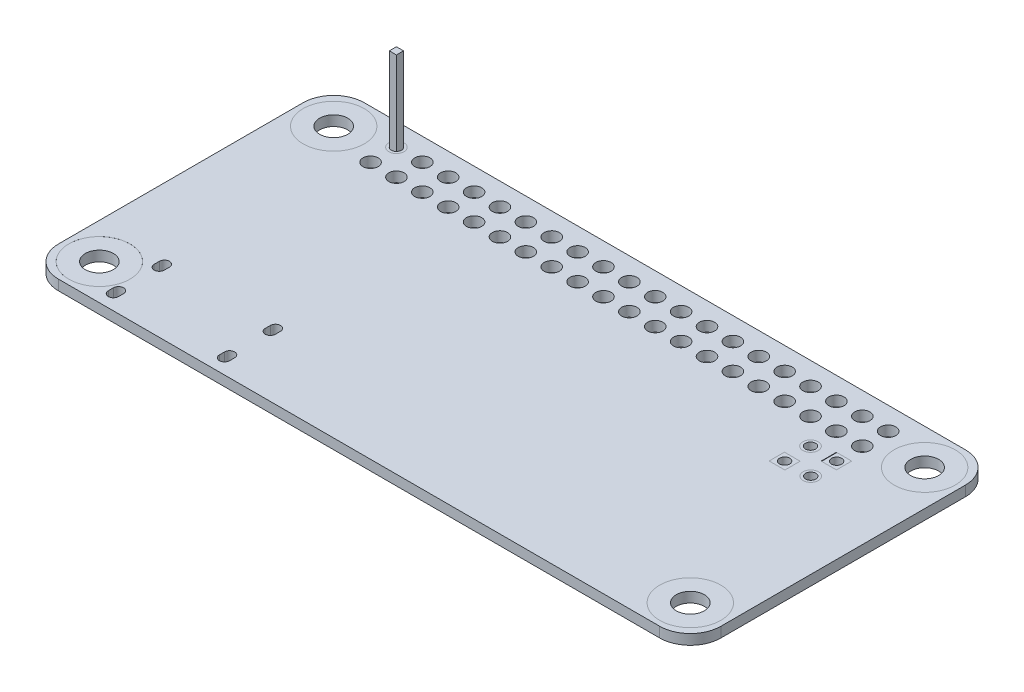
SolidWorks part; units mm, degrees
ref_plane "Front Plane" through (0, 0, 0) normal (0, 0, 1) x (1, 0, 0)
ref_plane "Top Plane" through (0, 0, 0) normal (0, 1, 0) x (1, 0, 0)
ref_plane "Right Plane" through (0, 0, 0) normal (1, 0, 0) x (0, 0, -1)
sketch "Sketch1" plane through (0, 0, 0) normal (0, 1, 0) x (1, 0, 0)
  line L0 (-27.4768, 39.9178) -> (-27.4768, -37.6558) construction
  line L1 (-29.5, -15) -> (29.5, -15)
  line L2 (-32.5, -12) -> (-32.5, 12)
  line L3 (-29.5, 15) -> (29.5, 15)
  line L4 (32.5, -12) -> (32.5, 12)
  line L5 (-32.5, -15) -> (32.5, 15) construction
  line L6 (-32.5, 15) -> (32.5, -15) construction
  line L7 (0, 0) -> (0, 39.9178) construction
  line L9 (-25.5, 14.1112) -> (25.5, 14.1112) construction
  line L10 (-25.5, 14.1112) -> (-25.5, 8.9112) construction
  line L11 (-25.5, 8.9112) -> (25.5, 8.9112) construction
  line L12 (25.5, 14.1112) -> (25.5, 8.9112) construction
  line L13 (23.38, 6.9577) -> (24.88, 6.9577)
  line L14 (23.38, 6.9577) -> (23.38, 8.4577)
  line L15 (23.38, 8.4577) -> (24.88, 8.4577)
  line L16 (24.88, 6.9577) -> (24.88, 8.4577)
  line L17 (23.38, 6.9577) -> (24.88, 8.4577) construction
  line L18 (23.38, 8.4577) -> (24.88, 6.9577) construction
  line L19 (20.8606, 4.4177) -> (22.3606, 4.4177)
  line L20 (20.8606, 4.4177) -> (20.8606, 5.9177)
  line L21 (20.8606, 5.9177) -> (22.3606, 5.9177)
  line L22 (22.3606, 4.4177) -> (22.3606, 5.9177)
  line L23 (20.8606, 4.4177) -> (22.3606, 5.9177) construction
  line L24 (20.8606, 5.9177) -> (22.3606, 4.4177) construction
  arc A0 (-32.5, 12) -> (-29.5, 15) centre (-29.5, 12) cw
  arc A1 (-29.5, -15) -> (-32.5, -12) centre (-29.5, -12) cw
  arc A2 (29.5, -15) -> (32.5, -12) centre (29.5, -12) ccw
  arc A3 (29.5, 15) -> (32.5, 12) centre (29.5, 12) cw
  circle A4 centre (-29, 11.5) radius 3
  circle A5 centre (-29, -11.5) radius 3
  circle A6 centre (29, -11.5) radius 3
  circle A7 centre (-24.13, 12.7877) radius 0.75
  circle A8 centre (-21.59, 12.7877) radius 0.75
  circle A9 centre (-19.05, 12.7877) radius 0.75
  circle A10 centre (-16.51, 12.7877) radius 0.75
  circle A11 centre (-13.97, 12.7877) radius 0.75
  circle A12 centre (-11.43, 12.7877) radius 0.75
  circle A13 centre (-8.89, 12.7877) radius 0.75
  circle A14 centre (-6.35, 12.7877) radius 0.75
  circle A15 centre (-3.81, 12.7877) radius 0.75
  circle A16 centre (-1.27, 12.7877) radius 0.75
  circle A17 centre (1.27, 12.7877) radius 0.75
  circle A18 centre (3.81, 12.7877) radius 0.75
  circle A19 centre (6.35, 12.7877) radius 0.75
  circle A20 centre (8.89, 12.7877) radius 0.75
  circle A21 centre (11.43, 12.7877) radius 0.75
  circle A22 centre (13.97, 12.7877) radius 0.75
  circle A23 centre (16.51, 12.7877) radius 0.75
  circle A24 centre (19.05, 12.7877) radius 0.75
  circle A25 centre (21.59, 12.7877) radius 0.75
  circle A26 centre (24.13, 12.7877) radius 0.75
  circle A27 centre (-21.59, 10.2477) radius 0.75
  circle A28 centre (-19.05, 10.2477) radius 0.75
  circle A29 centre (-16.51, 10.2477) radius 0.75
  circle A30 centre (-13.97, 10.2477) radius 0.75
  circle A31 centre (-11.43, 10.2477) radius 0.75
  circle A32 centre (-8.89, 10.2477) radius 0.75
  circle A33 centre (-6.35, 10.2477) radius 0.75
  circle A34 centre (-3.81, 10.2477) radius 0.75
  circle A35 centre (-1.27, 10.2477) radius 0.75
  circle A36 centre (1.27, 10.2477) radius 0.75
  circle A37 centre (3.81, 10.2477) radius 0.75
  circle A38 centre (6.35, 10.2477) radius 0.75
  circle A39 centre (8.89, 10.2477) radius 0.75
  circle A40 centre (11.43, 10.2477) radius 0.75
  circle A41 centre (13.97, 10.2477) radius 0.75
  circle A42 centre (16.51, 10.2477) radius 0.75
  circle A43 centre (19.05, 10.2477) radius 0.75
  circle A44 centre (21.59, 10.2477) radius 0.75
  circle A45 centre (24.13, 10.2477) radius 0.75
  circle A46 centre (-24.13, 10.2477) radius 0.75
  circle A47 centre (21.59, 7.7077) radius 0.75
  circle A48 centre (24.1506, 5.1677) radius 0.75
  circle A49 centre (29, 11.5) radius 3
  point P0 (0, 0)
  point P32 (0, 8.9112)
  point P117 (24.13, 7.7077)
  point P122 (21.6106, 5.1677)
  dimension "D3" = 3
  dimension "D4" = 51
  dimension "D5" = 6
  dimension "D11" = 1.5
  dimension "D12" = 2
  dimension "D15" = 1.5
  dimension "D16" = 1.5
  dimension "D27" = 6
  dimension "D28" = 6
  dimension "D1" = 65
  dimension "D2" = 30
  dimension "D6" = 23
  dimension "D7" = 29
  dimension "D8" = 3.5
  dimension "D9" = 5.2
  dimension "D10" = 29
  dimension "D13" = 1.27
  dimension "D14" = 20
  dimension "D17" = 2.54
  dimension "D18" = 2.54
  dimension "D19" = 2.54
  dimension "D20" = 2.54
  dimension "D21" = 2.54
  dimension "D22" = 2.54
  dimension "D23" = 1.5
  dimension "D24" = 1.5
  dimension "D25" = 1.5
  dimension "D26" = 1.5
extrude "Boss-Extrude1" add sketch "Sketch1" along normal blind 1
sketch "Sketch2" plane through (0, 0, 0) normal (0, 1, 0) x (1, 0, 0)
  circle A0 centre (-24.13, 12.7877) radius 0.75 construction
  circle A1 centre (-24.13, 12.7877) radius 0.75
  circle A3 centre (-24.13, 12.7877) radius 0.5
  dimension "D1" = 1
extrude "Boss-Extrude2" add sketch "Sketch2" along normal blind 1 separate body
sketch "Sketch6" plane through (0, 1, 0) normal (0, 1, 0) x (1, 0, 0)
  line L0 (-23.78, 12.4377) -> (-23.78, 13.1377)
  line L1 (-23.78, 12.4377) -> (-24.48, 12.4377)
  line L2 (-23.78, 13.1377) -> (-24.48, 13.1377)
  line L3 (-24.48, 12.4377) -> (-24.48, 13.1377)
  line L4 (-23.78, 12.4377) -> (-24.48, 13.1377) construction
  line L5 (-23.78, 13.1377) -> (-24.48, 12.4377) construction
  circle A0 centre (-24.13, 12.7877) radius 0.5 construction
  point P1 (-24.13, 12.7877)
  dimension "D1" = 0.7
extrude "Boss-Extrude5" add sketch "Sketch6" along normal blind 8.2 and the other way blind 3
pattern_linear "LPattern2" [suppressed] count 20 spacing 2.54 count 2 spacing 2.54 of bodies 153 102 101
sketch "Sketch3" plane through (0, 0, 0) normal (0, 1, 0) x (1, 0, 0)
  line L1 (20.8194, 4.4177) -> (22.3606, 4.4177)
  line L2 (20.8194, 4.4177) -> (20.8194, 5.9177)
  line L3 (20.8194, 5.9177) -> (22.3606, 5.9177)
  line L4 (22.3606, 4.4177) -> (22.3606, 5.9177)
  line L5 (20.8194, 4.4177) -> (22.3606, 5.9177) construction
  line L6 (20.8194, 5.9177) -> (22.3606, 4.4177) construction
  line L7 (23.4212, 6.9577) -> (24.88, 6.9577)
  line L8 (23.4212, 6.9577) -> (23.4212, 8.4577)
  line L9 (23.4212, 8.4577) -> (24.88, 8.4577)
  line L10 (24.88, 6.9577) -> (24.88, 8.4577)
  line L11 (23.4212, 6.9577) -> (24.88, 8.4577) construction
  line L12 (23.4212, 8.4577) -> (24.88, 6.9577) construction
  circle A0 centre (21.59, 7.7077) radius 0.75
  circle A1 centre (21.59, 7.7077) radius 0.5
  circle A2 centre (24.1506, 5.1677) radius 0.75
  circle A3 centre (24.1506, 5.1677) radius 0.5
  circle A4 centre (24.1506, 7.7077) radius 0.5
  circle A5 centre (21.59, 5.1677) radius 0.5
  dimension "D1" = 1
  dimension "D2" = 1
  dimension "D3" = 1
  dimension "D4" = 1
extrude "Boss-Extrude3" add sketch "Sketch3" along normal blind 1 separate body
sketch "Sketch4" plane through (0, 0, 0) normal (0, 1, 0) x (1, 0, 0)
  circle A0 centre (-29, 11.5) radius 3
  circle A1 centre (-29, 11.5) radius 1.375
  dimension "D1" = 2.75
extrude "Boss-Extrude4" add sketch "Sketch4" along normal blind 1 separate body
mirror "Mirror1" about plane through (0, 0, 0) normal (1, 0, 0) of bodies 147
mirror "Mirror2" about plane through (0, 0, 0) normal (0, 0, 1) of bodies 147 148
sketch "Sketch5" plane through (0, 0, 0) normal (0, -1, 0) x (1, 0, 0)
  line L0 (-25.5788, 13.0395) -> (-25.5788, 13.5395) construction
  line L1 (-26.0788, 13.0395) -> (-26.0788, 13.5395)
  line L2 (-25.0788, 13.0395) -> (-25.0788, 13.5395)
  line L3 (-14.6788, 13.0395) -> (-14.6788, 13.5395) construction
  line L4 (-15.1788, 13.0395) -> (-15.1788, 13.5395)
  line L5 (-14.1788, 13.0395) -> (-14.1788, 13.5395)
  line L6 (-14.6788, 8.5395) -> (-14.6788, 9.0395) construction
  line L7 (-15.1788, 8.5395) -> (-15.1788, 9.0395)
  line L8 (-14.1788, 8.5395) -> (-14.1788, 9.0395)
  line L9 (-25.5788, 8.5395) -> (-25.5788, 9.0395) construction
  line L10 (-26.0788, 8.5395) -> (-26.0788, 9.0395)
  line L11 (-25.0788, 8.5395) -> (-25.0788, 9.0395)
  arc A0 (-26.0788, 13.0395) -> (-25.0788, 13.0395) centre (-25.5788, 13.0395) ccw
  arc A1 (-25.0788, 13.5395) -> (-26.0788, 13.5395) centre (-25.5788, 13.5395) ccw
  arc A2 (-15.1788, 13.0395) -> (-14.1788, 13.0395) centre (-14.6788, 13.0395) ccw
  arc A3 (-14.1788, 13.5395) -> (-15.1788, 13.5395) centre (-14.6788, 13.5395) ccw
  arc A4 (-15.1788, 8.5395) -> (-14.1788, 8.5395) centre (-14.6788, 8.5395) ccw
  arc A5 (-14.1788, 9.0395) -> (-15.1788, 9.0395) centre (-14.6788, 9.0395) ccw
  arc A6 (-26.0788, 8.5395) -> (-25.0788, 8.5395) centre (-25.5788, 8.5395) ccw
  arc A7 (-25.0788, 9.0395) -> (-26.0788, 9.0395) centre (-25.5788, 9.0395) ccw
  point P2 (-25.5788, 13.2895)
  point P11 (-14.6788, 13.2895)
  point P18 (-14.6788, 8.7895)
  point P25 (-25.5788, 8.7895)
  dimension "D2" = 0.5
  dimension "D1" = 0.5
  dimension "D3" = 2
extrude "Cut-Extrude1" cut sketch "Sketch5" against normal blind 1
